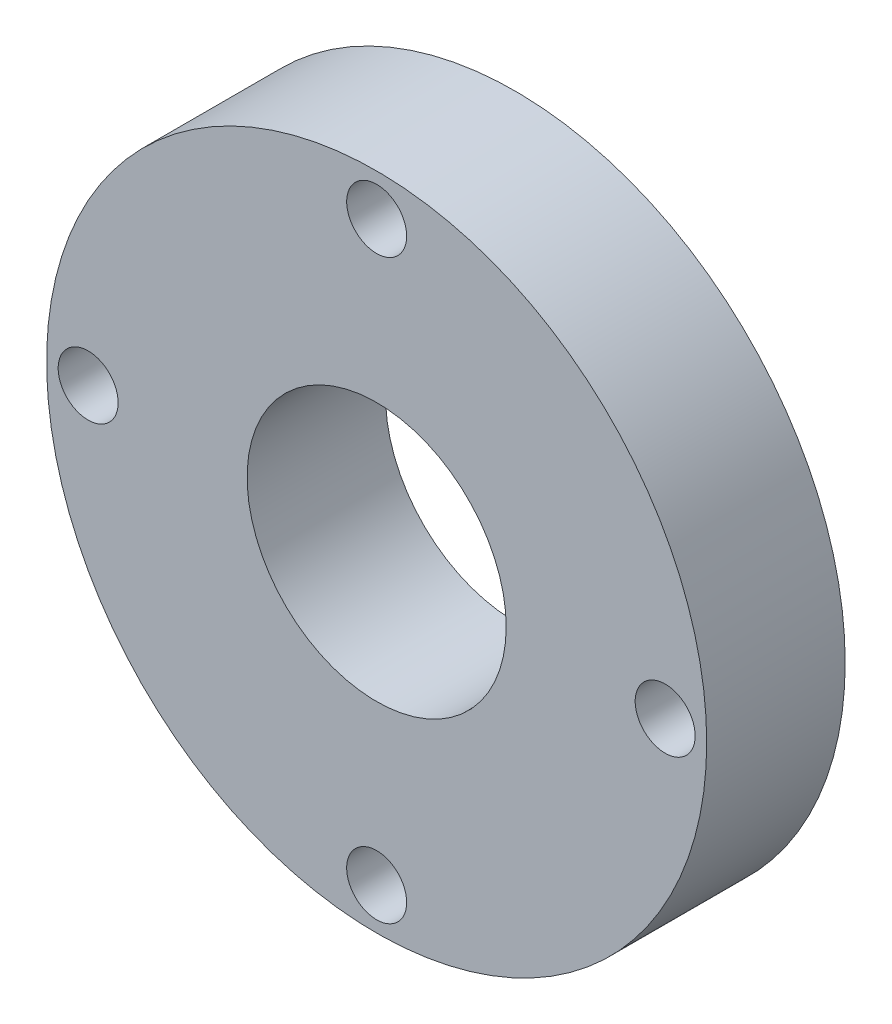
SolidWorks part; units mm, degrees
material "6061-T6 (SS)"
ref_plane "Front Plane" through (0, 0, 0) normal (0, 0, 1) x (1, 0, 0)
ref_plane "Top Plane" through (0, 0, 0) normal (0, 1, 0) x (1, 0, 0)
ref_plane "Right Plane" through (0, 0, 0) normal (1, 0, 0) x (0, 0, -1)
sketch "Sketch1" plane through (0, 0, 0) normal (1, 0, 0) x (0, 0, -1)
  line L0 (-95.847, -9.525) -> (-141.966, -9.525)
  line L5 (-1000, 0) -> (49000, 0)
  line L6 (0, -9.525) -> (0, 9.525)
  line L13 (0, 9.525) -> (-45.847, 9.525)
  line L26 (-45.847, 9.525) -> (-45.847, 12.7)
  line L27 (-45.847, 12.7) -> (-95.847, 12.7)
  line L32 (-95.847, 12.7) -> (-95.847, 9.525)
  line L34 (-160, 7) -> (-160, -7)
  line L36 (-95.847, -9.525) -> (-95.847, -12.7)
  line L37 (-95.847, -12.7) -> (-45.847, -12.7)
  line L38 (-45.847, -12.7) -> (-45.847, -9.525)
  line L39 (0, -9.525) -> (-45.847, -9.525)
  line L40 (-25.305, 36.322) -> (-16.305, 36.322)
  line L41 (-111.341, 22.6187) -> (-95.847, 22.6187)
  line L42 (-111.341, 22.6187) -> (-111.341, -22.6187)
  line L43 (-111.341, -22.6187) -> (-95.847, -22.6187)
  line L44 (-95.847, 22.6187) -> (-95.847, -22.6187)
  line L45 (-111.341, 22.6187) -> (-95.847, -22.6187) construction
  line L46 (-111.341, -22.6187) -> (-95.847, 22.6187) construction
  line L47 (-30.353, 22.6187) -> (-45.847, 22.6187)
  line L48 (-30.353, 22.6187) -> (-30.353, -22.6187)
  line L49 (-30.353, -22.6187) -> (-45.847, -22.6187)
  line L50 (-45.847, 22.6187) -> (-45.847, -22.6187)
  line L51 (-30.353, 22.6187) -> (-45.847, -22.6187) construction
  line L52 (-30.353, -22.6187) -> (-45.847, 22.6187) construction
  line L59 (-16.305, 36.322) -> (-16.305, -36.322)
  line L60 (-16.305, -36.322) -> (-25.305, -36.322)
  line L61 (-25.305, -22.6187) -> (-27.305, -22.6187)
  line L62 (-27.305, -22.6187) -> (-27.305, -12.5)
  line L63 (-27.305, -12.5) -> (-25.305, -12.5)
  line L64 (-25.305, -12.5) -> (-25.305, 12.5)
  line L65 (-25.305, 12.5) -> (-27.305, 12.5)
  line L66 (-27.305, 12.5) -> (-27.305, 22.6187)
  line L67 (-27.305, 22.6187) -> (-25.305, 22.6187)
  line L68 (-25.305, 22.6187) -> (-25.305, 36.322)
  line L69 (-25.305, -22.6187) -> (-25.305, -36.322)
  line L71 (-119.469, 36.322) -> (-26.305, 36.322)
  line L72 (-119.469, 36.322) -> (-119.469, -36.322)
  line L73 (-119.469, -36.322) -> (-26.305, -36.322)
  line L74 (-26.305, 36.322) -> (-26.305, -36.322)
  line L75 (-119.469, 36.322) -> (-26.305, -36.322) construction
  line L76 (-119.469, -36.322) -> (-26.305, 36.322) construction
  line L78 (-147.3, -7) -> (-160, -7)
  line L79 (-95.847, 9.525) -> (-141.966, 9.525)
  line L80 (-147.3, 7) -> (-160, 7)
  line L82 (-118.9065, 9.525) -> (-118.9065, -9.525) construction
  line L83 (-22.9235, 9.525) -> (-22.9235, -9.525) construction
  line L96 (-119.469, 36.322) -> (-134.709, 36.322)
  line L98 (-119.469, -36.322) -> (-134.709, -36.322)
  line L99 (-134.709, 36.322) -> (-134.709, -36.322)
  line L110 (-119.469, 36.322) -> (-119.469, -36.322)
  line L111 (-147.3, 7) -> (-147.3, 7.493)
  line L112 (-147.3, 7.493) -> (-141.966, 7.493)
  line L113 (-141.966, 7.493) -> (-141.966, 9.525)
  line L114 (-141.966, -9.525) -> (-141.966, -7.493)
  line L115 (-141.966, -7.493) -> (-147.3, -7.493)
  line L116 (-147.3, -7.493) -> (-147.3, -7)
  point P3 (0, 0)
  point P18 (-103.594, 0)
  point P24 (-38.1, 0)
  point P29 (-72.887, 0)
  point P48 (-16.305, 30.4704)
  point P60 (-16.305, 30.4704)
  point P70 (-134.709, 31.75)
revolve "Main_body" add sketch "Sketch1" angle 360 about L5 region at (0, 22.9235, 127.089)
sketch "Sketch5" plane through (0, 0, 134.709) normal (0, 0, 1) x (1, 0, 0)
  circle A0 centre (0, 0) radius 14.2558
  dimension "D1" = 28.5115
extrude "seal_seat" cut sketch "Sketch5" against normal through all
hole_wizard "M6 Clearance Hole1" positions "Sketch3" profile "Sketch4" hole size "M6" standard "ANSI Metric" end condition through all
sketch "Sketch3" plane through (0, 0, 134.709) normal (0, 0, 1) x (1, 0, 0)
  point P0 (0, 31.75)
sketch "Sketch4" plane through (0, 31.75, 134.709) normal (1, 0, 0) x (0, -1, 0)
  line L0 (0, 0) -> (0, 15.24)
  line L1 (0, 15.24) -> (3.3, 15.24)
  line L2 (3.3, 15.24) -> (3.3, 0)
  line L5 (3.3, 0) -> (0, 0)
  line L11 (0, -6.35) -> (0, 107.95) construction
  dimension "Thru Hole Dia." = 6.6
  dimension "Thru Hole Depth" = 15.24
pattern_circular "CirPattern1" count 4 over 360 about axis through (0, 0, 1000) along (0, 0, -1) of "M6 Clearance Hole1"
